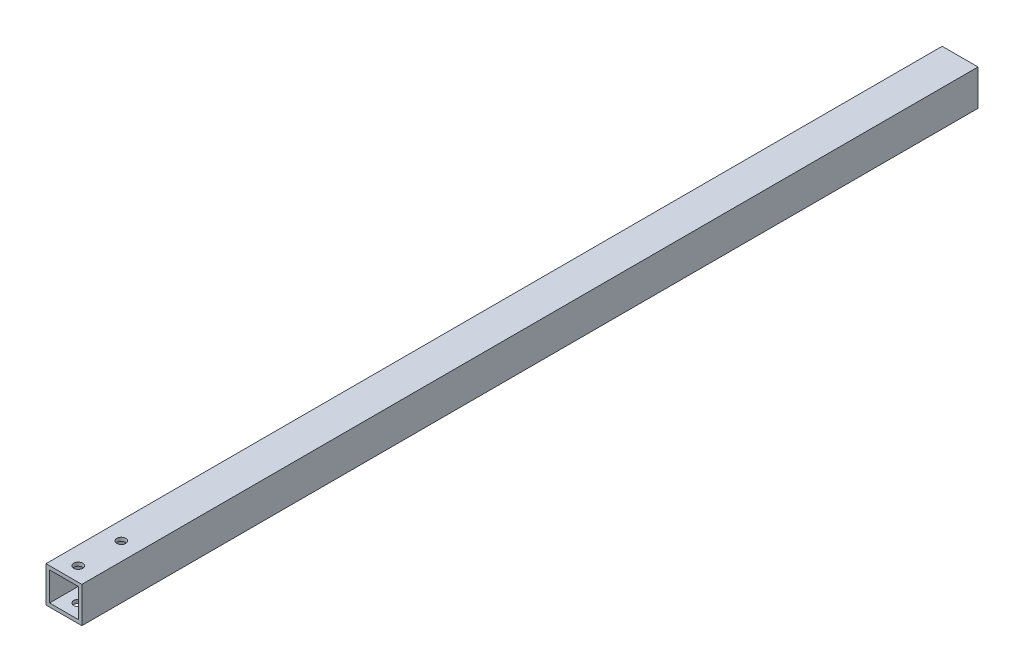
SolidWorks part; units mm, degrees
material "Thornel Mat VMA"
ref_plane "前视基准面" through (0, 0, 0) normal (0, 0, 1) x (1, 0, 0)
ref_plane "上视基准面" through (0, 0, 0) normal (0, 1, 0) x (1, 0, 0)
ref_plane "右视基准面" through (0, 0, 0) normal (1, 0, 0) x (0, 0, -1)
sketch "草图1" plane through (0, 0, 0) normal (0, 0, 1) x (1, 0, 0)
  line L1 (5, 5) -> (-5, 5)
  line L2 (5, 5) -> (5, -5)
  line L3 (5, -5) -> (-5, -5)
  line L4 (-5, 5) -> (-5, -5)
  line L5 (5, 5) -> (-5, -5) construction
  line L6 (5, -5) -> (-5, 5) construction
  line L7 (4, 4) -> (-4, 4)
  line L8 (4, 4) -> (4, -4)
  line L9 (4, -4) -> (-4, -4)
  line L10 (-4, 4) -> (-4, -4)
  line L11 (4, 4) -> (-4, -4) construction
  line L12 (4, -4) -> (-4, 4) construction
  point P0 (0, 0)
  point P6 (0, 0)
  dimension "D1" = 10
  dimension "D2" = 1
extrude "凸台-拉伸1" add sketch "草图1" along normal blind 250
hole_wizard "孔1" positions "草图2" profile "草图3" legacy end condition through all
sketch "草图2" plane through (0, -5, 0) normal (0, -1, 0) x (-1, 0, 0)
  point P0 (0, -246)
  point P3 (0, -234)
sketch "草图3" plane through (0, -5, 246) normal (1, 0, 0) x (0, 0, -1)
  line L0 (0, 0) -> (0, 10)
  line L1 (0, 10) -> (1.25, 10)
  line L2 (1.25, 10) -> (1.25, 0)
  line L3 (1.25, 0) -> (0, 0)
  line L4 (0, 110) -> (0, -10) construction
  dimension "直径" = 2.5
  dimension "深度" = 10
